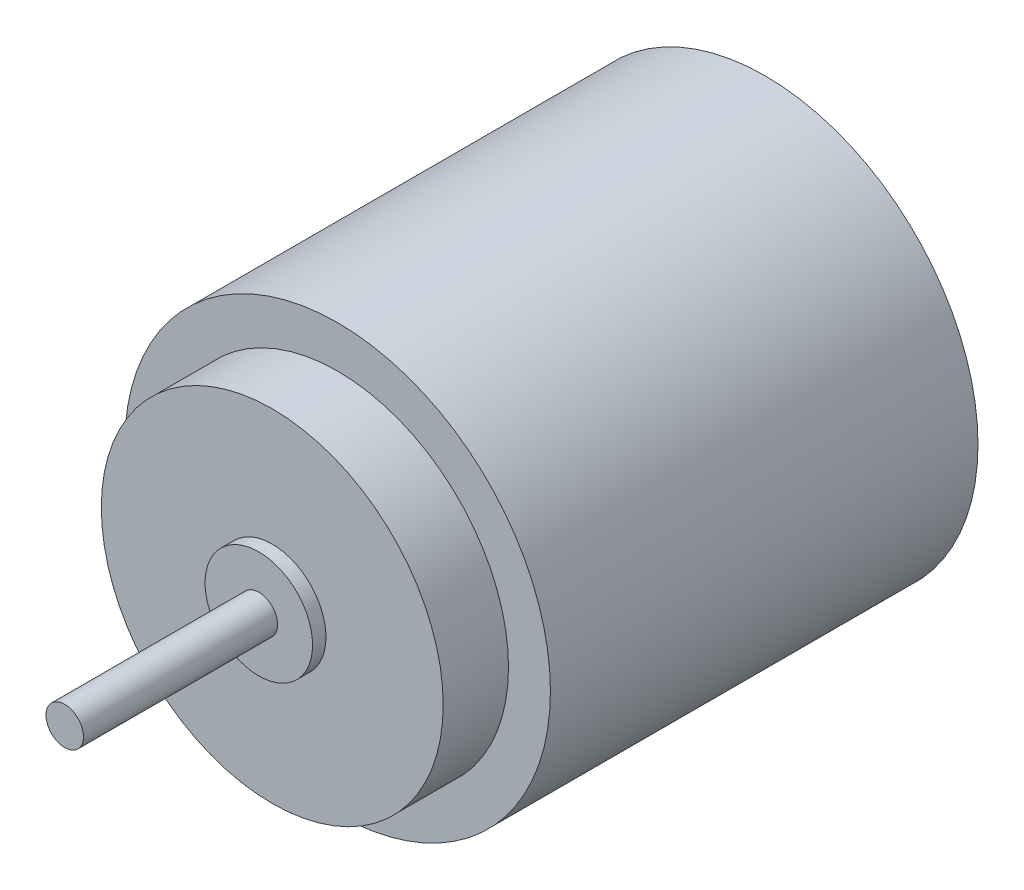
SolidWorks part; units mm, degrees
ref_plane "Front Plane" through (0, 0, 0) normal (0, 0, 1) x (1, 0, 0)
ref_plane "Top Plane" through (0, 0, 0) normal (0, 1, 0) x (1, 0, 0)
ref_plane "Right Plane" through (0, 0, 0) normal (1, 0, 0) x (0, 0, -1)
sketch "Sketch1" plane through (0, 0, 0) normal (0, 0, 1) x (1, 0, 0)
  circle A0 centre (0, 0) radius 11.6713
  dimension "D1" = 23.3426
extrude "Boss-Extrude1" add sketch "Sketch1" along normal blind 23.4442 contours A0
sketch "Sketch4" plane through (0, 0, 23.4442) normal (0, 0, 1) x (1, 0, 0)
  circle A0 centre (0, 0) radius 9.3726
  dimension "D1" = 18.7452
extrude "Boss-Extrude3" add sketch "Sketch4" along normal blind 3.5814
sketch "Sketch5" plane through (0, 0, 27.0256) normal (0, 0, 1) x (1, 0, 0)
  circle A0 centre (0, 0) radius 2.9464
  dimension "D1" = 5.8928
extrude "Boss-Extrude4" add sketch "Sketch5" along normal blind 0.7366
sketch "Sketch2" plane through (0, 0, 27.7622) normal (0, 0, 1) x (1, 0, 0)
  circle A0 centre (0, 0) radius 1.0287
  dimension "D1" = 2.0574
extrude "Boss-Extrude2" add sketch "Sketch2" along normal blind 10.6426
equation "\"MotorLength\"=0.923"
equation "\"MotorDiameter\"=0.919"
equation "\"ShaftLength\"=0.419"
equation "\"ShaftDiameter\" = 0.081"
equation "\"D1@Sketch1\"= \"MotorDiameter\""
equation "\"D1@Boss-Extrude1\"= \"MotorLength\""
equation "\"D1@Sketch2\"= \"ShaftDiameter\""
equation "\"D1@Boss-Extrude2\"= \"ShaftLength\""
